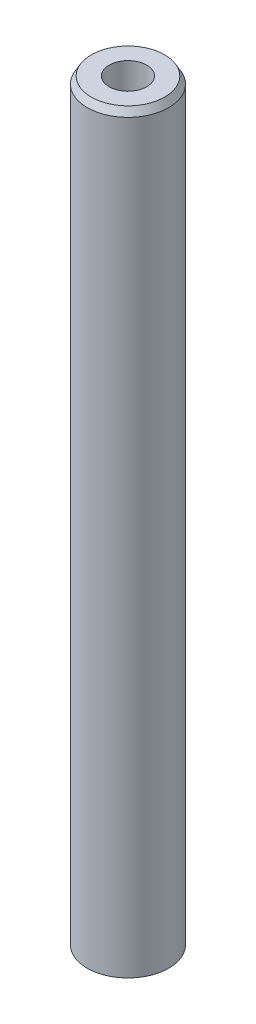
SolidWorks part; units mm, degrees
ref_plane "Front Plane" through (0, 0, 0) normal (0, 0, 1) x (1, 0, 0)
ref_plane "Top Plane" through (0, 0, 0) normal (0, 1, 0) x (1, 0, 0)
ref_plane "Right Plane" through (0, 0, 0) normal (1, 0, 0) x (0, 0, -1)
sketch "Sketch1" plane through (0, 0, 0) normal (0, 1, 0) x (1, 0, 0)
  circle A0 centre (0, 0) radius 7.5
  dimension "SHAFT_OD" = 15
extrude "Boss-Extrude1" add sketch "Sketch1" along normal blind 139.2428
sketch "Sketch2" plane through (0, 0, 0) normal (0, 1, 0) x (1, 0, 0)
  circle A0 centre (0, 0) radius 3.4589
  dimension "BORE_D" = 6.9177
extrude "Cut-Extrude1" cut sketch "Sketch2" along normal through all
chamfer "Chamfer1" distance 1.3011 angle 30 2 edges at (0, 139.2428, 7.5) (0, 0, 7.5) first distance on face at (0, 139.2428, 7.5) first distance on face at (0, 0, 3.4589)
